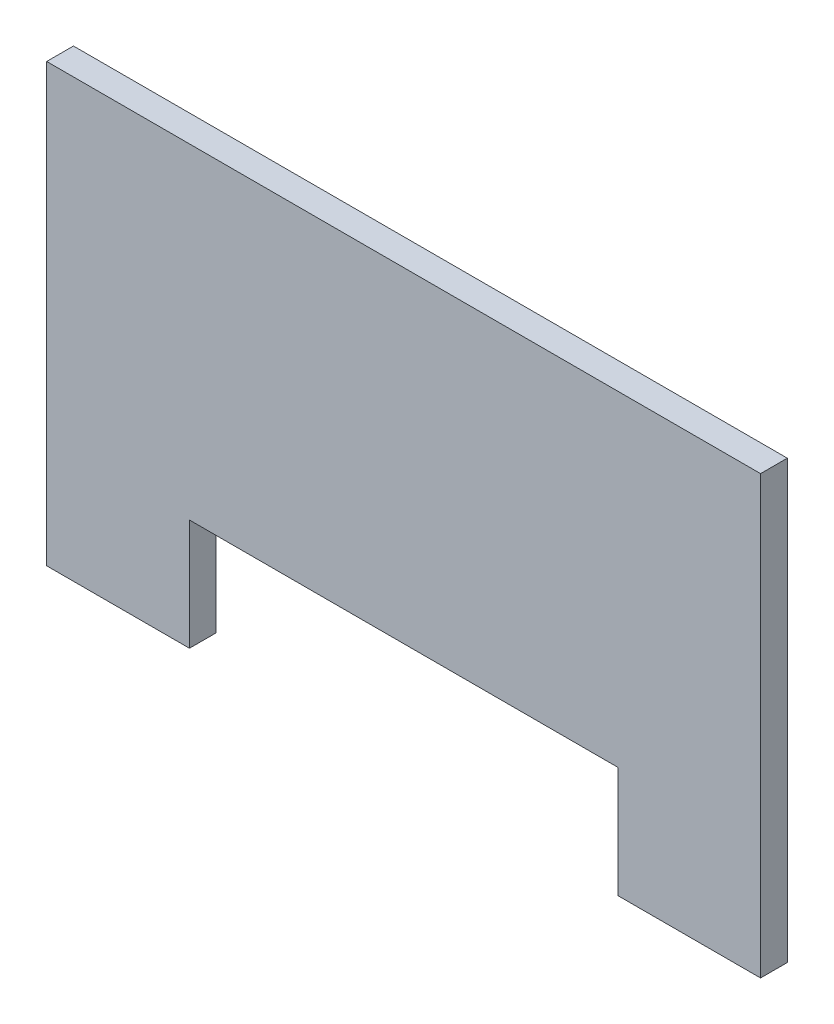
SolidWorks part; units mm, degrees
ref_plane "Front Plane" through (0, 0, 0) normal (0, 0, 1) x (1, 0, 0)
ref_plane "Top Plane" through (0, 0, 0) normal (0, 1, 0) x (1, 0, 0)
ref_plane "Right Plane" through (0, 0, 0) normal (1, 0, 0) x (0, 0, -1)
sketch "Sketch1" plane through (0, 0, 0) normal (0, 0, 1) x (1, 0, 0)
  line L0 (80, 3.175) -> (0, 3.175) construction
  line L1 (0, 52.125) -> (80, 52.125)
  line L2 (0, 52.125) -> (0, 3.175)
  line L3 (0, 3.175) -> (80, 3.175) construction
  line L4 (80, 52.125) -> (80, 3.175)
  line L5 (80, 52.125) -> (0, 52.125) construction
  line L6 (0, 52.125) -> (0, 3.175) construction
  line L7 (80, 52.125) -> (80, 3.175) construction
  line L8 (3, 49.125) -> (77, 49.125) construction
  line L9 (77, 49.125) -> (77, 6.175) construction
  line L10 (3, 6.175) -> (77, 6.175) construction
  line L11 (3, 49.125) -> (3, 6.175) construction
  line L12 (77, 49.125) -> (3, 49.125) construction
  line L13 (0, 18.625) -> (80, 18.625) construction
  line L14 (0, 15.625) -> (80, 15.625) construction
  line L15 (0, 40.925) -> (80, 40.925) construction
  line L16 (0, 37.925) -> (80, 37.925) construction
  line L17 (0, 37.925) -> (80, 37.925) construction
  line L18 (0, 40.925) -> (80, 40.925) construction
  line L19 (0, 15.625) -> (80, 15.625) construction
  line L20 (80, 18.625) -> (0, 18.625) construction
  line L21 (16, 3.175) -> (16, 15.625)
  line L22 (16, 15.625) -> (64, 15.625)
  line L23 (64, 15.625) -> (64, 3.175)
  line L24 (16, 3.175) -> (16, 15.625) construction
  line L25 (64, 15.625) -> (64, 3.175) construction
  line L26 (16, 3.175) -> (0, 3.175)
  line L27 (64, 3.175) -> (80, 3.175)
  circle A0 centre (37.5, 29.175) radius 21 construction
  circle A1 centre (37.5, 29.175) radius 24 construction
  circle A2 centre (37.5, 29.175) radius 24 construction
  circle A3 centre (37.5, 29.175) radius 21 construction
sketch "Sketch2" plane through (0, 0, 0) normal (1, 0, 0) x (0, 0, -1)
  line L1 (0, 52.125) -> (3, 52.125)
  line L2 (0, 52.125) -> (0, 3.175)
  line L3 (0, 3.175) -> (3, 3.175)
  line L4 (3, 52.125) -> (3, 3.175)
extrude "Boss-Extrude1" add sketch "Sketch1" against normal up to vertex (3 mm away) up to point (0, 52.125, -3)
